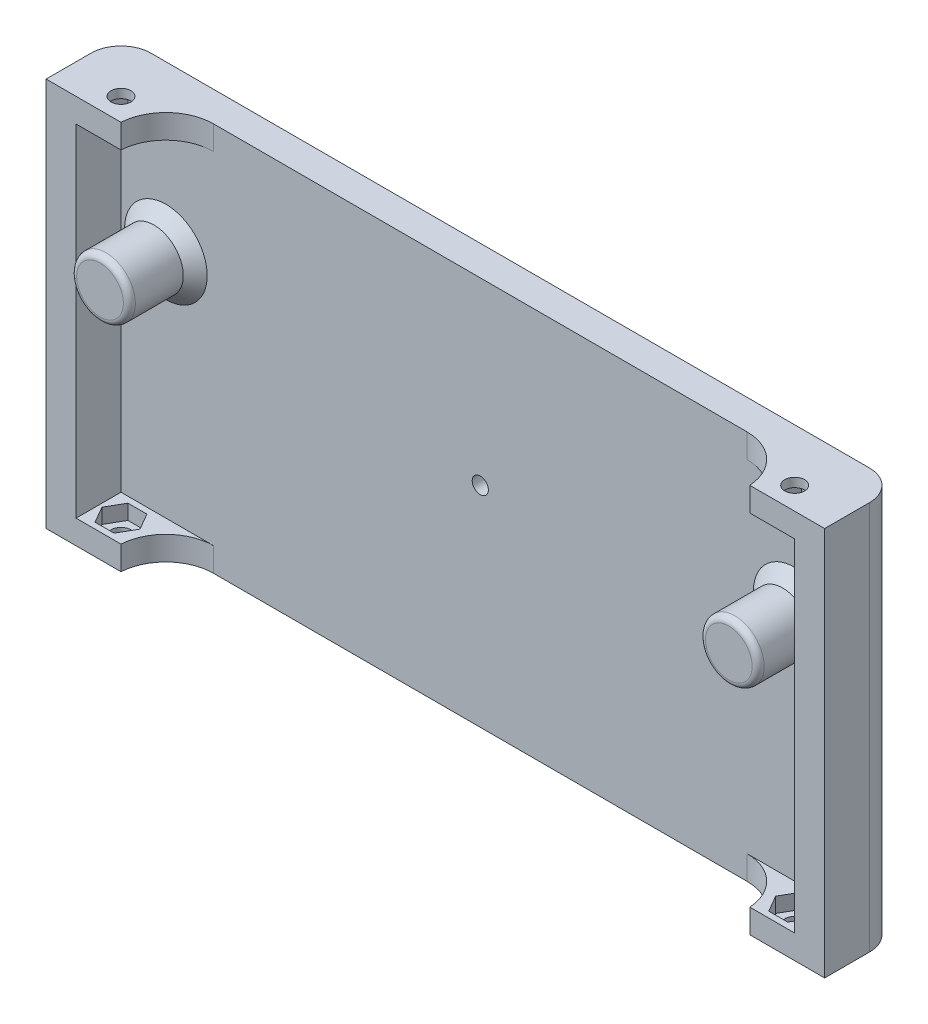
SolidWorks part; units mm, degrees
ref_plane "Front Plane" through (0, 0, 0) normal (0, 0, 1) x (1, 0, 0)
ref_plane "Top Plane" through (0, 0, 0) normal (0, 1, 0) x (1, 0, 0)
ref_plane "Right Plane" through (0, 0, 0) normal (1, 0, 0) x (0, 0, -1)
sketch "Sketch1" plane through (0, 0, 0) normal (0, 0, 1) x (1, 0, 0)
  line L1 (0, 0) -> (130, 0)
  line L2 (0, 0) -> (0, 65)
  line L3 (0, 65) -> (130, 65)
  line L4 (130, 0) -> (130, 65)
  dimension "D1" = 65
  dimension "D2" = 130
extrude "Boss-Extrude1" add sketch "Sketch1" along normal blind 12.5
sketch "Sketch3" plane through (0, 65, 0) normal (0, 1, 0) x (1, 0, 0)
  line L0 (5, -12.5) -> (125, -12.5)
  line L9 (125, -5) -> (125, -12.5)
  line L10 (5, -5) -> (125, -5)
  line L11 (5, -12.5) -> (5, -5)
  line L12 (125, -5) -> (125, -12.5)
  line L13 (5, -5) -> (125, -5)
  line L14 (5, -12.5) -> (5, -5)
  dimension "D1" = 5
extrude "Cut-Extrude1" cut sketch "Sketch3" against normal through all
fillet "Fillet1" radius 5 2 edges at (130, 32.5, 0) (0, 32.5, 0)
sketch "Sketch4" plane through (0, 0, 0) normal (0, -1, 0) x (1, 0, 0)
  line L0 (125, 5) -> (5, 5) construction
  line L1 (5, 12.5) -> (12.5, 12.5)
  line L2 (5, 12.5) -> (5, 5)
  line L3 (5, 5) -> (12.5, 5)
  line L4 (12.5, 12.5) -> (12.5, 5)
  line L6 (125, 5) -> (117.5, 5)
  line L7 (125, 5) -> (125, 12.5)
  line L8 (125, 12.5) -> (117.5, 12.5)
  line L9 (117.5, 5) -> (117.5, 12.5)
extrude "Boss-Extrude2" add sketch "Sketch4" against normal blind 4
sketch "Sketch5" plane through (0, 4, 0) normal (0, 1, 0) x (1, 0, 0)
  line L0 (121.25, -5) -> (121.25, -12.5) construction
  line L1 (117.5, -5) -> (125, -5) construction
  line L2 (125, -12.5) -> (117.5, -12.5) construction
  line L3 (65, 0) -> (65, -12.5) construction
  line L4 (124.4254, -8.75) -> (122.8377, -6)
  line L5 (122.8377, -6) -> (119.6623, -6)
  line L6 (119.6623, -6) -> (118.0746, -8.75)
  line L7 (118.0746, -8.75) -> (119.6623, -11.5)
  line L8 (119.6623, -11.5) -> (122.8377, -11.5)
  line L9 (122.8377, -11.5) -> (124.4254, -8.75)
  line L10 (125, 0) -> (5, 0) construction
  line L11 (10.3377, -6) -> (11.9254, -8.75)
  line L12 (11.9254, -8.75) -> (10.3377, -11.5)
  line L13 (7.1623, -11.5) -> (5.5746, -8.75)
  line L14 (10.3377, -11.5) -> (7.1623, -11.5)
  line L15 (7.1623, -6) -> (10.3377, -6)
  line L16 (5.5746, -8.75) -> (7.1623, -6)
  circle A0 centre (121.25, -8.75) radius 2.75 construction
  circle A1 centre (121.25, -8.75) radius 1.65
  circle A2 centre (8.75, -8.75) radius 1.65
  dimension "D2" = 3.3
  dimension "D1" = 5.5
extrude "Cut-Extrude2" cut sketch "Sketch5" against normal blind 2.5
extrude "Cut-Extrude3" cut sketch "Sketch5<3>" against normal through all contours A2 | A1 region at (121.25, 4, 8.75) region at (8.75, 4, 8.75)
sketch "Sketch5<3>" plane through (0, 4, 0) normal (0, 1, 0) x (1, 0, 0) same geometry as "Sketch5"
fillet "Fillet2" radius 8 2 edges at (117.5, 2, 5) (12.5, 2, 5)
ref_plane "Plane1" through (0, 32.5, 0) normal (0, 1, 0) x (1, 0, 0)
mirror "Mirror1" about plane through (0, 32.5, 0) normal (0, 1, 0) of "Cut-Extrude3", "Cut-Extrude2", "Boss-Extrude2", "Fillet2"
sketch "Sketch7" plane through (0, 0, 5) normal (0, 0, 1) x (1, 0, 0)
  line L0 (130, 0) -> (117.5, 0) construction
  line L1 (109.5156, 0) -> (20.4844, 0) construction
  line L2 (117.5, 0) -> (117.5, 42.5) construction
  line L3 (65, 65) -> (65, 0) construction
  line L4 (109.5156, 65) -> (20.4844, 65) construction
  circle A0 centre (117.5, 42.5) radius 4.9
  circle A1 centre (12.5, 42.5) radius 4.9
  dimension "D3" = 9.8
  dimension "D1" = 12.5
  dimension "D2" = 42.5
extrude "Boss-Extrude3" add sketch "Sketch7" along normal blind 11
fillet "Fillet3" radius 1 2 edges at (122.4, 42.5, 16) (7.6, 42.5, 16)
chamfer "Chamfer1" distance 2 angle 45 2 edges at (112.6, 42.5, 5) (7.6, 42.5, 5)
sketch "Sketch8" plane through (0, 0, 0) normal (0, 0, -1) x (-1, 0, 0)
  line L0 (-65, 65) -> (-65, 35) construction
  line L1 (-125, 65) -> (-5, 65) construction
  circle A0 centre (-65, 35) radius 1.35
  dimension "D2" = 2.7
  dimension "D1" = 30
extrude "Cut-Extrude4" cut sketch "Sketch8" against normal through all
